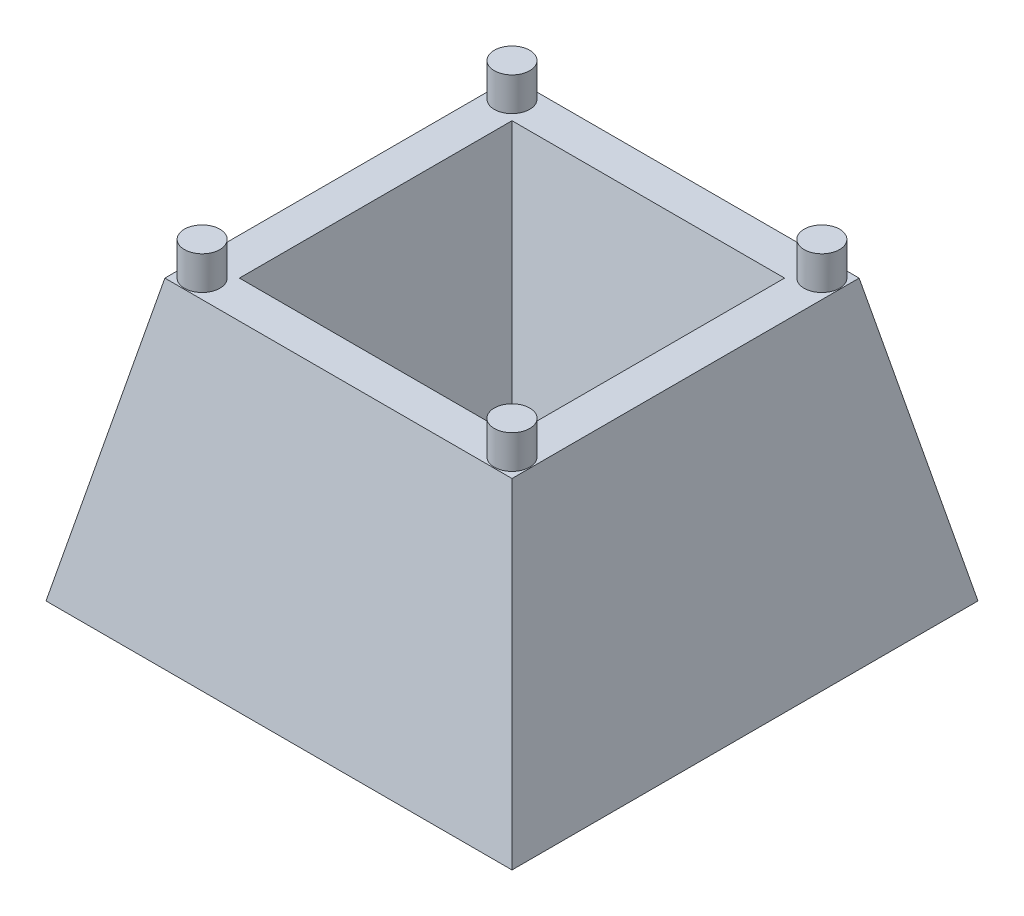
SolidWorks part; units mm, degrees
ref_plane "Front Plane" through (0, 0, 0) normal (0, 0, 1) x (1, 0, 0)
ref_plane "Top Plane" through (0, 0, 0) normal (0, 1, 0) x (1, 0, 0)
ref_plane "Right Plane" through (0, 0, 0) normal (1, 0, 0) x (0, 0, -1)
sketch "Sketch4" plane through (0, 0, 0) normal (0, 1, 0) x (1, 0, 0)
  line L0 (0, 12.5) -> (0, -12.5) construction
  line L4 (12.5, 12.5) -> (12.5, -12.5)
  line L8 (-12.5, 12.5) -> (-12.5, -12.5)
  line L9 (-12.5, 0) -> (12.5, 0) construction
  line L10 (-12.5, 12.5) -> (12.5, 12.5)
  line L11 (-12.5, -12.5) -> (12.5, -12.5)
  point P11 (0, 12.5)
  dimension "D1" = 25
  dimension "D3" = 25
extrude "Base" add sketch "Sketch4" along normal blind 15 draft 12
sketch "Sketch5" plane through (0, 15, 0) normal (0, 1, 0) x (1, 0, 0)
  line L8 (-7.3117, 7.3117) -> (-7.3117, -7.3117)
  line L13 (-9.3117, 9.3117) -> (-9.3117, -9.3117) construction
  line L16 (-7.3117, 7.3117) -> (7.3117, 7.3117)
  line L17 (-7.3117, -7.3117) -> (7.3117, -7.3117)
  line L18 (7.3117, 7.3117) -> (7.3117, -7.3117)
  line L19 (0, 9.3117) -> (0, 7.3117) construction
  line L20 (9.3117, 9.3117) -> (-9.3117, 9.3117) construction
  line L21 (7.3117, 0) -> (9.3117, 0) construction
  line L22 (9.3117, -9.3117) -> (9.3117, 9.3117) construction
  line L23 (0, -7.3117) -> (0, -9.3117) construction
  line L24 (-9.3117, -9.3117) -> (9.3117, -9.3117) construction
  line L25 (-9.3117, 0) -> (-7.3117, 0) construction
  line L26 (-9.3117, 9.3117) -> (-9.3117, -9.3117) construction
  dimension "D2" = 2
extrude "Reservoir" cut sketch "Sketch5" against normal blind 12 draft 12
sketch "Sketch1" plane through (0, 3, 0) normal (0, 1, 0) x (1, 0, 0)
  line L25 (-4.761, 0) -> (4.761, 0) construction
  line L26 (-4.761, 4.761) -> (-4.761, -4.761) construction
  line L27 (4.761, -4.761) -> (4.761, 4.761) construction
  line L30 (0, 4.761) -> (0, -4.761) construction
  line L31 (4.761, 4.761) -> (-4.761, 4.761) construction
  line L32 (-4.761, -4.761) -> (4.761, -4.761) construction
  line L51 (1.78, 0) -> (1.78, 1.75) construction
  line L53 (-0.6722, 0.2) -> (-0.8714, 0.5451)
  line L57 (-0.75, 0.075) -> (0.75, 0.075) construction
  line L59 (-0.4557, 0.075) -> (0.4557, 0.075)
  line L62 (-0.8317, 0.8469) -> (-0.1768, 1.5018)
  line L64 (0.6722, 0.2) -> (0.8714, 0.5451)
  line L65 (0.8317, 0.8469) -> (0.1768, 1.5018)
  line L66 (0.6722, -0.2) -> (0.8714, -0.5451)
  line L67 (0.8317, -0.8469) -> (0.1768, -1.5018)
  line L68 (-0.8317, -0.8469) -> (-0.1768, -1.5018)
  line L69 (-0.6722, -0.2) -> (-0.8714, -0.5451)
  line L70 (-0.4557, -0.075) -> (0.4557, -0.075)
  circle A208 centre (-3.78, 0) radius 0.75
  circle A219 centre (3.78, 0) radius 0.75
  circle A224 centre (1.78, 0) radius 1
  circle A229 centre (-1.78, 0) radius 1
  circle A240 centre (2.93, 1.75) radius 0.75
  circle A241 centre (2.93, -1.75) radius 0.75
  circle A244 centre (-2.93, -1.75) radius 0.75
  circle A245 centre (-2.93, 1.75) radius 0.75
  arc A246 (-0.6722, 0.2) -> (-0.4557, 0.075) centre (-0.4557, 0.325) ccw
  arc A247 (-0.8714, 0.5451) -> (-0.8317, 0.8469) centre (-0.6549, 0.6701) cw
  arc A248 (0.6722, 0.2) -> (0.4557, 0.075) centre (0.4557, 0.325) cw
  arc A249 (0.8714, 0.5451) -> (0.8317, 0.8469) centre (0.6549, 0.6701) ccw
  arc A250 (-0.1768, 1.5018) -> (0.1768, 1.5018) centre (0, 1.325) cw
  arc A251 (0.8714, -0.5451) -> (0.8317, -0.8469) centre (0.6549, -0.6701) cw
  arc A252 (-0.1768, -1.5018) -> (0.1768, -1.5018) centre (0, -1.325) ccw
  arc A253 (-0.8714, -0.5451) -> (-0.8317, -0.8469) centre (-0.6549, -0.6701) ccw
  arc A254 (-0.6722, -0.2) -> (-0.4557, -0.075) centre (-0.4557, -0.325) cw
  arc A255 (0.6722, -0.2) -> (0.4557, -0.075) centre (0.4557, -0.325) ccw
  circle A256 centre (1.03, 2) radius 0.75
  circle A257 centre (1.03, -2) radius 0.75
  circle A258 centre (-1.03, 2) radius 0.75
  circle A259 centre (-1.03, -2) radius 0.75
  point P5 (0, 0.075)
  point P25 (-0.6, 0.075)
  point P37 (0, 0.075)
  point P48 (0, 1.6786)
  dimension "D3" = 1.15
  dimension "D4" = 1.5
  dimension "D2" = 2
  dimension "D5" = 0.075
  dimension "D6" = 1.5
  dimension "D7" = 0.15
  dimension "D9" = 0.25
  dimension "D13" = 1.78
  dimension "D10" = 2
  dimension "D12" = 1.5
  dimension "D11" = 0.25
  dimension "D15" = 2
  dimension "D16" = 2
  dimension "D19" = 2
  dimension "D20" = 1.25
  dimension "D8" = 120
  dimension "D14" = 1.78
  dimension "D17" = 1.75
  dimension "D18" = 0.75
extrude "Pillars" add sketch "Sketch1" along normal blind 1.5 draft 12 contours A208 | A245 | A244 | A241 | A240 | A219 | A258 | A256 | A257 | A259 region at (-3.78, 3, 0) region at (3.78, 3, 0) region at (2.93, 3, -1.75) region at (2.93, 3, 1.75) region at (-2.93, 3, 1.75) region at (-2.93, 3, -1.75)
extrude "Channel Walls" add sketch "Sketch1<10>" along normal blind 0.5 draft 12 contours L66 A255 L70 A254 L69 A253 L68 A252 L67 A251 | A250 L62 A247 L53 A246 L59 A248 L64 A249 L65 region at (0, 3, -0.712) region at (0, 3, 0.712)
sketch "Sketch1<10>" plane through (0, 3, 0) normal (0, 1, 0) x (1, 0, 0) same geometry as "Sketch1"
sketch "Sketch11" plane through (0, 15, 0) normal (0, 1, 0) x (1, 0, 0)
  line L0 (-9.3117, 8.3117) -> (9.3117, 8.3117) construction
  line L1 (-9.3117, 9.3117) -> (-9.3117, -9.3117) construction
  line L2 (9.3117, -9.3117) -> (9.3117, 9.3117) construction
  line L3 (8.3117, 9.3117) -> (8.3117, -9.3117) construction
  line L6 (7.3117, 7.3117) -> (-7.3117, 7.3117) construction
  line L7 (9.3117, 9.3117) -> (-9.3117, 9.3117) construction
  line L8 (0, 9.3117) -> (0, 7.3117) construction
  line L10 (9.3117, 0) -> (7.3117, 0) construction
  line L12 (7.3117, -7.3117) -> (7.3117, 7.3117) construction
  line L13 (9.3117, -9.3117) -> (9.3117, 9.3117) construction
  circle A0 centre (8.3117, 8.3117) radius 0.95
  circle A1 centre (-8.3117, 8.3117) radius 0.95
  circle A2 centre (-8.3117, -8.3117) radius 0.95
  circle A3 centre (8.3117, -8.3117) radius 0.95
  point P24 (0, 8.3117)
  point P25 (8.3117, 0)
  dimension "D1" = 1.9
extrude "Pegs" add sketch "Sketch11" along normal blind 1.8
sketch "Sketch12" plane through (0, 3, 0) normal (0, 1, 0) x (1, 0, 0)
  line L0 (0, 0.075) -> (0, -0.075) construction
  line L1 (-0.4557, 0.075) -> (0.4557, 0.075) construction
  line L2 (-0.4557, -0.075) -> (0.4557, -0.075) construction
  line L3 (-0.78, 0) -> (0.78, 0) construction
  line L5 (-0.4557, 0.1813) -> (0.4557, 0.1813) construction
  line L6 (-0.4557, -0.1813) -> (0.4557, -0.1813) construction
  line L7 (0.4557, -0.1813) -> (0.4557, -0.075) construction
  line L8 (-0.5801, -0.2531) -> (-0.7794, -0.5982) construction
  circle A0 centre (1.78, 0) radius 1
  circle A2 centre (-1.78, 0) radius 1
  dimension "D1" = 2
  dimension "D6" = 0.3626
  dimension "D2" = 1.78
  dimension "D3" = 1.56
  dimension "D4" = 120
  dimension "D5" = 0.15
  dimension "D7" = 0.9113
sketch "Sketch13" plane through (0, 0, 0) normal (1, 0, 0) x (0, 0, -1)
  line L0 (1.4799, 3.5076) -> (1.4918, 3.0092) construction
  line L1 (2.4648, 4.5044) -> (2.4648, 3.0092) construction
  line L2 (0.0797, 3.0092) -> (-0.075, 3.0092) construction
  line L3 (0.1747, 3.5076) -> (-0.1932, 3.5076) construction
  dimension "D1" = 1.4951
  dimension "D2" = 0.4984
  dimension "D3" = 0.1547
  dimension "D4" = 0.3679
